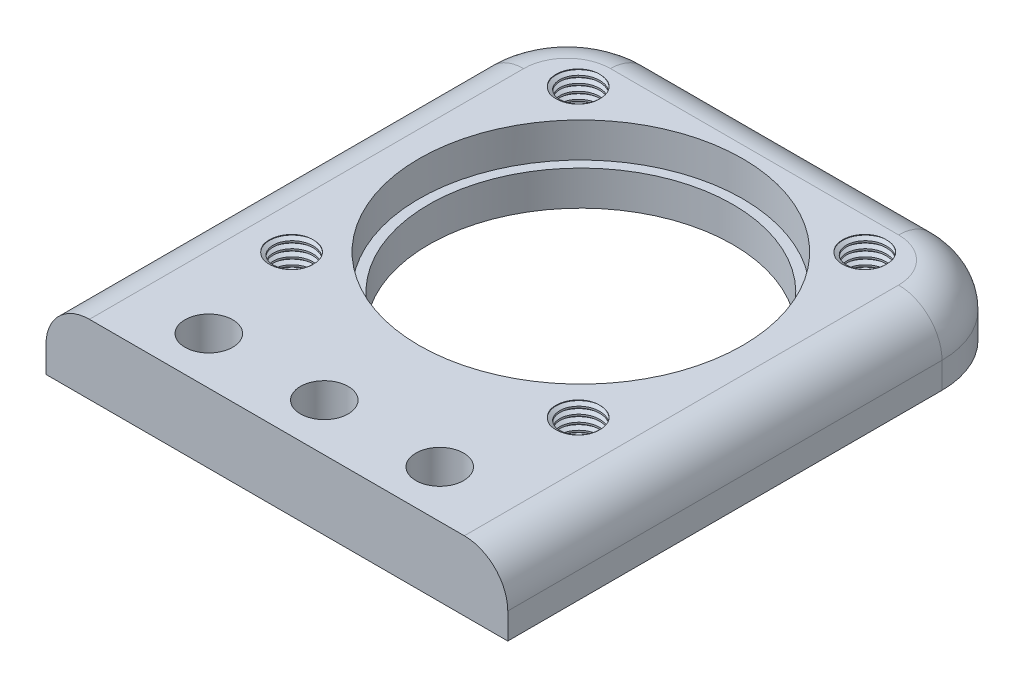
SolidWorks part; units mm, degrees
ref_plane "Front Plane" through (0, 0, 0) normal (0, 0, 1) x (1, 0, 0)
ref_plane "Top Plane" through (0, 0, 0) normal (0, 1, 0) x (1, 0, 0)
ref_plane "Right Plane" through (0, 0, 0) normal (1, 0, 0) x (0, 0, -1)
sketch "Sketch1" plane through (0, 0, 0) normal (0, 1, 0) x (1, 0, 0)
  line L1 (0, 0) -> (53.17, 0)
  line L2 (0, 0) -> (0, 60)
  line L3 (0, 60) -> (53.17, 60)
  line L4 (53.17, 0) -> (53.17, 60)
  circle A0 centre (26.585, 35) radius 18.63
  circle A1 centre (26.585, 5.4571) radius 2.75
  circle A2 centre (13.29, 5.4571) radius 2.75
  circle A3 centre (39.88, 5.4571) radius 2.75
  dimension "D3" = 26.585
  dimension "D5" = 26.585
  dimension "D1" = 53.17
  dimension "D2" = 60
  dimension "D4" = 25
  dimension "D6" = 13.295
  dimension "D7" = 13.295
extrude "Boss-Extrude1" add sketch "Sketch1" along normal blind 8
fillet "Fillet1" radius 10 2 edges at (53.17, 4, -60) (0, 4, -60)
fillet "Fillet2" radius 5 5 edges at (50.2411, 8, -57.0711) (26.585, 8, -60) (2.9289, 8, -57.0711) (53.17, 8, -25) (0, 8, -25)
sketch "Sketch2" plane through (0, 0, 0) normal (0, -1, 0) x (1, 0, 0)
  circle A0 centre (26.585, -35) radius 18.63
  circle A1 centre (26.585, -35) radius 17.5
extrude "Boss-Extrude2" add sketch "Sketch2" against normal blind 4
sketch "Sketch5" plane through (0, 8, 0) normal (0, 1, 0) x (1, 0, 0)
  line L1 (43.085, 18.5) -> (10.085, 18.5)
  line L2 (43.085, 18.5) -> (43.085, 51.5)
  line L3 (43.085, 51.5) -> (10.085, 51.5)
  line L4 (10.085, 18.5) -> (10.085, 51.5)
  line L5 (43.085, 18.5) -> (10.085, 51.5) construction
  line L6 (43.085, 51.5) -> (10.085, 18.5) construction
  circle A0 centre (10.085, 51.5) radius 2.3
  circle A1 centre (43.085, 51.5) radius 2.3
  circle A2 centre (43.085, 18.5) radius 2.3
  circle A3 centre (10.085, 18.5) radius 2.3
  point P0 (26.585, 35)
  dimension "D1" = 33
  dimension "D2" = 33
extrude "Cut-Extrude1" cut sketch "Sketch5" against normal blind 6 contours L3 A0 L4 | L4 A0 L3 | L2 A1 L3 | L1 A2 L2 | L4 A3 L1 | L1 A3 L4 | L2 A2 L1 region at (9.7596, 8, -18.1746) region at (11.0612, 8, -19.4762) region at (42.1088, 8, -19.4762) region at (43.4104, 8, -18.1746) region at (9.7596, 8, -51.8254) region at (11.0612, 8, -50.5238) region at (43.4104, 8, -51.8254)
thread "Thread1" pitch 0.8 method cut profile "Thread Profile1" start angle 0, offset 1, length 0, pitch 0.8, diameter 4.6
ref_plane "Plane1" through (7.785, 9, -51.5) normal (0, 0, 1) x (-1, 0, 0)
sketch "Thread Profile1" plane through (7.785, 9, -51.5) normal (0, 0, 1) x (-1, 0, 0)
  line L0 (0, 0) -> (0, 0.8) construction
  line L1 (0, 0) -> (0.433, 0.25)
  line L2 (0.433, 0.25) -> (0.433, 0.35)
  line L3 (0.433, 0.35) -> (0, 0.6)
  line L4 (0.433, 0.3) -> (0, 0.3) construction
  line L11 (0, 0) -> (0, 0.6)
  point P2 (0, 0)
  dimension "Pitch" = 0.8
  dimension "Profile_Angle" = 60
  dimension "Profile_Land" = 0.1
  dimension "Profile_Height" = 0.433
thread "Thread2" pitch 0.8 method cut profile "Thread Profile2" start angle 0, offset 1, length 0, pitch 0.8, diameter 4.6
ref_plane "Plane2" through (40.785, 9, -18.5) normal (0, 0, 1) x (-1, 0, 0)
sketch "Thread Profile2" plane through (40.785, 9, -18.5) normal (0, 0, 1) x (-1, 0, 0)
  line L0 (0, 0) -> (0, 0.8) construction
  line L1 (0, 0) -> (0.433, 0.25)
  line L2 (0.433, 0.25) -> (0.433, 0.35)
  line L3 (0.433, 0.35) -> (0, 0.6)
  line L4 (0.433, 0.3) -> (0, 0.3) construction
  line L11 (0, 0) -> (0, 0.6)
  point P2 (0, 0)
  dimension "Pitch" = 0.8
  dimension "Profile_Angle" = 60
  dimension "Profile_Land" = 0.1
  dimension "Profile_Height" = 0.433
thread "Thread3" pitch 0.8 method cut profile "Thread Profile3" start angle 0, offset 1, length 0, pitch 0.8, diameter 4.6
ref_plane "Plane3" through (7.785, 9, -18.5) normal (0, 0, 1) x (-1, 0, 0)
sketch "Thread Profile3" plane through (7.785, 9, -18.5) normal (0, 0, 1) x (-1, 0, 0)
  line L0 (0, 0) -> (0, 0.8) construction
  line L1 (0, 0) -> (0.433, 0.25)
  line L2 (0.433, 0.25) -> (0.433, 0.35)
  line L3 (0.433, 0.35) -> (0, 0.6)
  line L4 (0.433, 0.3) -> (0, 0.3) construction
  line L11 (0, 0) -> (0, 0.6)
  point P2 (0, 0)
  dimension "Pitch" = 0.8
  dimension "Profile_Angle" = 60
  dimension "Profile_Land" = 0.1
  dimension "Profile_Height" = 0.433
extrude "Cut-Extrude2" cut sketch "Sketch5<3>" against normal blind 6 contours L3 A1 L2 region at (42.1088, 8, -50.5238)
sketch "Sketch5<3>" plane through (0, 8, 0) normal (0, 1, 0) x (1, 0, 0) same geometry as "Sketch5"
thread "Thread4" pitch 0.8 method cut profile "Thread Profile4" start angle 0, offset 1, length 0, pitch 0.8, diameter 4.6
ref_plane "Plane4" through (40.785, 9, -51.5) normal (0, 0, 1) x (-1, 0, 0)
sketch "Thread Profile4" plane through (40.785, 9, -51.5) normal (0, 0, 1) x (-1, 0, 0)
  line L0 (0, 0) -> (0, 0.8) construction
  line L1 (0, 0) -> (0.433, 0.25)
  line L2 (0.433, 0.25) -> (0.433, 0.35)
  line L3 (0.433, 0.35) -> (0, 0.6)
  line L4 (0.433, 0.3) -> (0, 0.3) construction
  line L11 (0, 0) -> (0, 0.6)
  point P2 (0, 0)
  dimension "Pitch" = 0.8
  dimension "Profile_Angle" = 60
  dimension "Profile_Land" = 0.1
  dimension "Profile_Height" = 0.433
